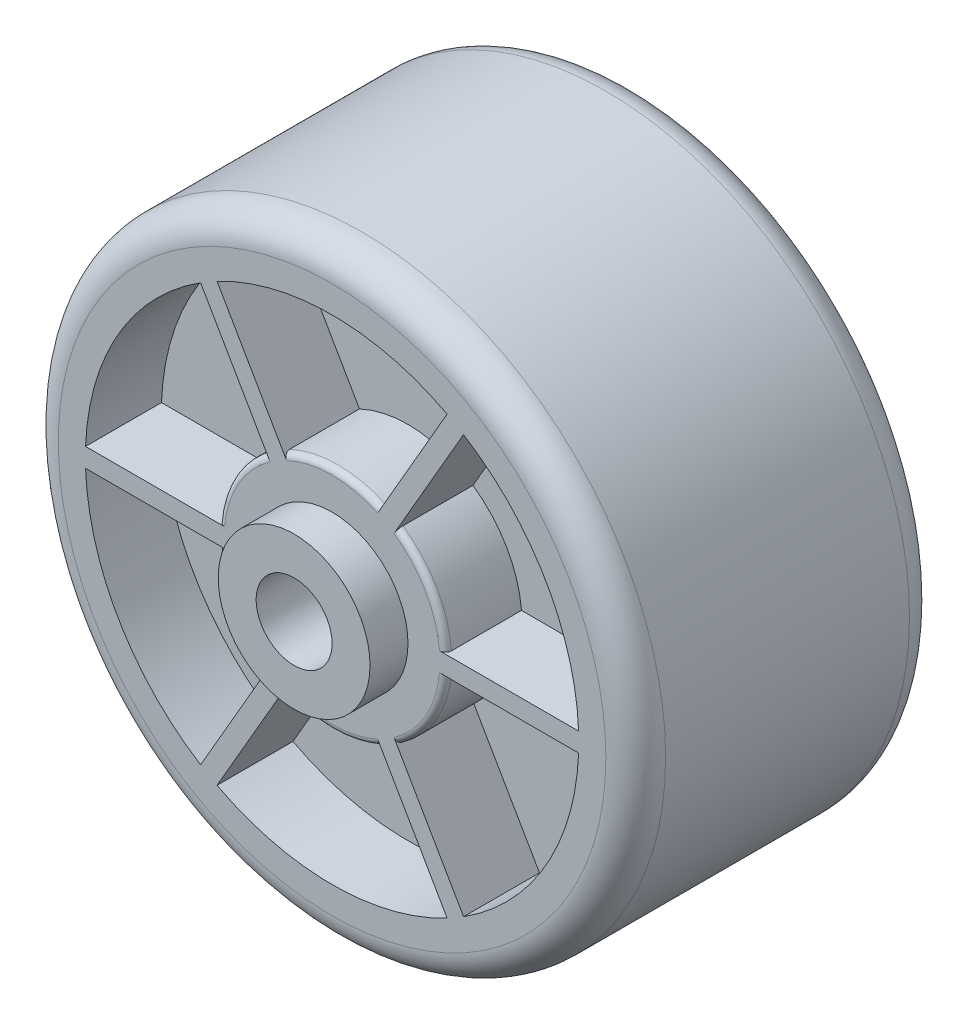
SolidWorks part; units mm, degrees
ref_plane "Front Plane" through (0, 0, 0) normal (0, 0, 1) x (1, 0, 0)
ref_plane "Top Plane" through (0, 0, 0) normal (0, 1, 0) x (1, 0, 0)
ref_plane "Right Plane" through (0, 0, 0) normal (1, 0, 0) x (0, 0, -1)
sketch "Sketch1" plane through (0, 0, 0) normal (0, 0, 1) x (1, 0, 0)
  circle A0 centre (0, 0) radius 50.8
  dimension "D1" = 101.6
extrude "Boss-Extrude1" add sketch "Sketch1" along normal blind 25.4 and the other way blind 25.4
sketch "Sketch3" plane through (0, 0, 25.4) normal (0, 0, 1) x (1, 0, 0)
  line L0 (-20.6375, 35.7452) -> (20.6375, -35.7452) construction
  line L1 (20.6375, 35.7452) -> (-20.6375, -35.7452) construction
  line L2 (-41.275, 0) -> (41.275, 0) construction
  line L12 (-19.2474, -36.5125) -> (-8.1171, -17.2342)
  line L13 (-21.997, -34.925) -> (-10.8667, -15.6467)
  line L15 (21.997, -34.925) -> (10.8667, -15.6467)
  line L16 (-21.997, 34.925) -> (-10.8667, 15.6467)
  line L20 (41.2445, -1.5875) -> (18.9837, -1.5875)
  line L21 (41.2445, 1.5875) -> (18.9837, 1.5875)
  line L22 (10.8667, 15.6467) -> (21.997, 34.925)
  line L23 (-8.1171, 17.2342) -> (-19.2474, 36.5125)
  line L24 (-18.9837, 1.5875) -> (-41.2445, 1.5875)
  line L25 (-18.9837, -1.5875) -> (-41.2445, -1.5875)
  line L26 (8.1171, 17.2342) -> (19.2474, 36.5125)
  line L27 (8.1171, -17.2342) -> (19.2474, -36.5125)
  arc A0 (-8.1171, -17.2342) -> (8.1171, -17.2342) centre (0, 0) ccw
  arc A1 (-21.997, 34.925) -> (-41.2445, 1.5875) centre (0, 0) ccw
  arc A2 (-18.9837, -1.5875) -> (-10.8667, -15.6467) centre (0, 0) ccw
  arc A3 (-10.8667, 15.6467) -> (-18.9837, 1.5875) centre (0, 0) ccw
  arc A4 (8.1171, 17.2342) -> (-8.1171, 17.2342) centre (0, 0) ccw
  arc A5 (18.9837, 1.5875) -> (10.8667, 15.6467) centre (0, 0) ccw
  arc A6 (10.8667, -15.6467) -> (18.9837, -1.5875) centre (0, 0) ccw
  arc A7 (19.2474, 36.5125) -> (-19.2474, 36.5125) centre (0, 0) ccw
  arc A8 (41.2445, 1.5875) -> (21.997, 34.925) centre (0, 0) ccw
  arc A9 (21.997, -34.925) -> (41.2445, -1.5875) centre (0, 0) ccw
  arc A10 (-19.2474, -36.5125) -> (19.2474, -36.5125) centre (0, 0) ccw
  arc A11 (-41.2445, -1.5875) -> (-21.997, -34.925) centre (0, 0) ccw
  point P1 (0, 0)
  point P10 (0, 0)
  point P13 (-20.6375, 35.7452)
  point P16 (0, 0)
  point P17 (-20.6375, 35.7452)
  point P20 (20.6375, 35.7452)
  point P23 (0, 0)
  point P26 (-20.6375, -35.7452)
  point P28 (0, 0)
  point P32 (0, 0)
  point P34 (20.6375, -35.7452)
  point P35 (0, 0)
  point P36 (-41.275, 0)
  point P37 (0, 0)
  point P38 (0, 0)
  point P39 (0, 0)
  point P40 (0, 0)
  point P41 (41.275, 0)
  point P45 (0, 0)
  point P46 (0, 0)
  point P52 (0, 0)
  point P53 (0, 0)
  point P54 (0, 0)
  point P56 (20.6375, 35.7452)
  point P57 (20.639, 35.7478)
  point P58 (0, 0)
  point P59 (0, 0)
  point P60 (0, 0)
  point P61 (-41.275, 0)
  point P62 (-41.2445, 0)
  point P63 (0, 0)
  point P64 (0, 0)
  point P65 (0, 0)
  point P66 (0, 0)
  point P67 (0, 0)
  point P68 (0, 0)
  point P69 (0, 0)
  point P70 (0, 0)
  point P71 (0, 0)
  point P72 (0, 0)
  point P73 (0, 0)
  point P74 (0, 0)
  dimension "D1" = 38.1
  dimension "D2" = 82.55
  dimension "D3" = 60
  dimension "D4" = 60
  dimension "D5" = 3.175
extrude "Cut-Extrude1" cut sketch "Sketch3" against normal blind 12.7
sketch "Sketch4" plane through (0, 0, -25.4) normal (0, 0, -1) x (-1, 0, 0)
  line L0 (21.997, -34.925) -> (10.8667, -15.6467) construction
  line L1 (18.9837, -1.5875) -> (41.2445, -1.5875) construction
  line L2 (8.1171, -17.2342) -> (19.2474, -36.5125) construction
  line L3 (-19.2474, -36.5125) -> (-8.1171, -17.2342) construction
  line L4 (-10.8667, -15.6467) -> (-21.997, -34.925) construction
  line L5 (-41.2445, -1.5875) -> (-18.9837, -1.5875) construction
  line L6 (-21.997, 34.925) -> (-10.8667, 15.6467) construction
  line L7 (-18.9837, 1.5875) -> (-41.2445, 1.5875) construction
  line L8 (41.2445, 1.5875) -> (18.9837, 1.5875) construction
  line L9 (10.8667, 15.6467) -> (21.997, 34.925) construction
  line L10 (-8.1171, 17.2342) -> (-19.2474, 36.5125) construction
  line L11 (19.2474, 36.5125) -> (8.1171, 17.2342) construction
  line L12 (21.997, -34.925) -> (10.8667, -15.6467)
  line L13 (18.9837, -1.5875) -> (41.2445, -1.5875)
  line L14 (8.1171, -17.2342) -> (19.2474, -36.5125)
  line L15 (-19.2474, -36.5125) -> (-8.1171, -17.2342)
  line L16 (-10.8667, -15.6467) -> (-21.997, -34.925)
  line L17 (-41.2445, -1.5875) -> (-18.9837, -1.5875)
  line L18 (-21.997, 34.925) -> (-10.8667, 15.6467)
  line L19 (-18.9837, 1.5875) -> (-41.2445, 1.5875)
  line L20 (41.2445, 1.5875) -> (18.9837, 1.5875)
  line L21 (10.8667, 15.6467) -> (21.997, 34.925)
  line L22 (-8.1171, 17.2342) -> (-19.2474, 36.5125)
  line L23 (19.2474, 36.5125) -> (8.1171, 17.2342)
  arc A0 (21.997, -34.925) -> (41.2445, -1.5875) centre (0, 0) ccw construction
  arc A1 (10.8667, -15.6467) -> (18.9837, -1.5875) centre (0, 0) ccw construction
  arc A2 (-8.1171, -17.2342) -> (8.1171, -17.2342) centre (0, 0) ccw construction
  arc A3 (-19.2474, -36.5125) -> (19.2474, -36.5125) centre (0, 0) ccw construction
  arc A4 (-18.9837, -1.5875) -> (-10.8667, -15.6467) centre (0, 0) ccw construction
  arc A5 (-41.2445, -1.5875) -> (-21.997, -34.925) centre (0, 0) ccw construction
  arc A6 (-21.997, 34.925) -> (-41.2445, 1.5875) centre (0, 0) ccw construction
  arc A7 (-10.8667, 15.6467) -> (-18.9837, 1.5875) centre (0, 0) ccw construction
  arc A8 (41.2445, 1.5875) -> (21.997, 34.925) centre (0, 0) ccw construction
  arc A9 (18.9837, 1.5875) -> (10.8667, 15.6467) centre (0, 0) ccw construction
  arc A10 (8.1171, 17.2342) -> (-8.1171, 17.2342) centre (0, 0) ccw construction
  arc A11 (19.2474, 36.5125) -> (-19.2474, 36.5125) centre (0, 0) ccw construction
  arc A12 (21.997, -34.925) -> (41.2445, -1.5875) centre (0, 0) ccw
  arc A13 (10.8667, -15.6467) -> (18.9837, -1.5875) centre (0, 0) ccw
  arc A14 (-8.1171, -17.2342) -> (8.1171, -17.2342) centre (0, 0) ccw
  arc A15 (-19.2474, -36.5125) -> (19.2474, -36.5125) centre (0, 0) ccw
  arc A16 (-18.9837, -1.5875) -> (-10.8667, -15.6467) centre (0, 0) ccw
  arc A17 (-41.2445, -1.5875) -> (-21.997, -34.925) centre (0, 0) ccw
  arc A18 (-21.997, 34.925) -> (-41.2445, 1.5875) centre (0, 0) ccw
  arc A19 (-10.8667, 15.6467) -> (-18.9837, 1.5875) centre (0, 0) ccw
  arc A20 (41.2445, 1.5875) -> (21.997, 34.925) centre (0, 0) ccw
  arc A21 (18.9837, 1.5875) -> (10.8667, 15.6467) centre (0, 0) ccw
  arc A22 (8.1171, 17.2342) -> (-8.1171, 17.2342) centre (0, 0) ccw
  arc A23 (19.2474, 36.5125) -> (-19.2474, 36.5125) centre (0, 0) ccw
extrude "Cut-Extrude2" cut sketch "Sketch4" against normal blind 12.7
sketch "Sketch5" plane through (0, 0, -25.4) normal (0, 0, -1) x (-1, 0, 0)
  circle A0 centre (0, 0) radius 12.7
  dimension "D1" = 25.4
extrude "Boss-Extrude2" add sketch "Sketch5" along normal blind 6.35
sketch "Sketch6" plane through (0, 0, 25.4) normal (0, 0, 1) x (1, 0, 0)
  circle A1 centre (0, 0) radius 50.8
  circle A2 centre (0, 0) radius 50.8
  circle A3 centre (0, 0) radius 12.7
  circle A4 centre (0, 0) radius 12.7
  dimension "D1" = 0
  dimension "D2" = 0
extrude "Boss-Extrude3" add sketch "Sketch6" along normal blind 6.35 contours A4
sketch "Sketch7" plane through (0, 0, 31.75) normal (0, 0, 1) x (1, 0, 0)
  circle A0 centre (0, 0) radius 6.35
  dimension "D1" = 12.7
extrude "Cut-Extrude3" cut sketch "Sketch7" against normal through all
fillet "Fillet1" radius 5 2 edges at (50.8, 0, 25.4) (50.8, 0, -25.4)
fillet "Fillet2" radius 1 12 edges at (16.4978, 9.525, 25.4) (16.4978, -9.525, 25.4) (0, -19.05, 25.4) (-16.4978, -9.525, 25.4) (0, 19.05, 25.4) (-16.4978, 9.525, 25.4) (-16.4978, 9.525, -25.4) (-16.4978, -9.525, -25.4) (0, -19.05, -25.4) (16.4978, -9.525, -25.4) (16.4978, 9.525, -25.4) (0, 19.05, -25.4)
